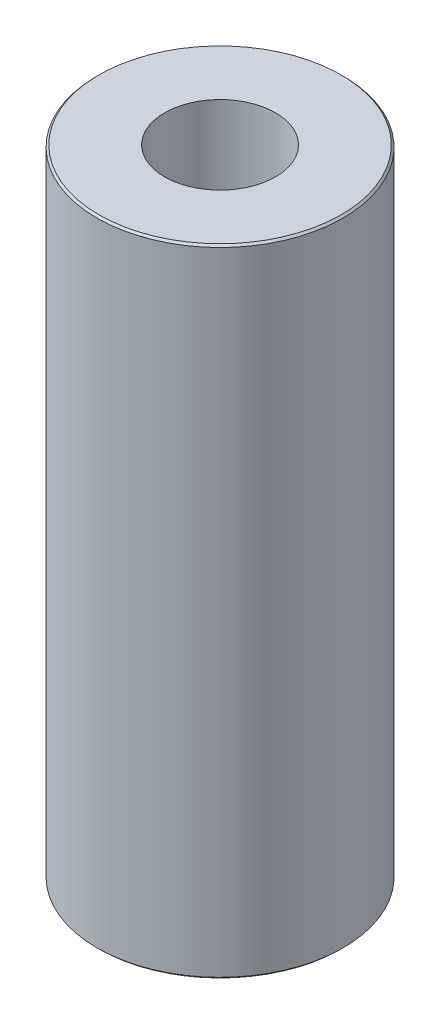
SolidWorks part; units mm, degrees
ref_plane "Front Plane" through (0, 0, 0) normal (0, 0, 1) x (1, 0, 0)
ref_plane "Top Plane" through (0, 0, 0) normal (0, 1, 0) x (1, 0, 0)
ref_plane "Right Plane" through (0, 0, 0) normal (1, 0, 0) x (0, 0, -1)
sketch "Sketch1" plane through (0, 0, 0) normal (0, 1, 0) x (1, 0, 0)
  circle A0 centre (0, 0) radius 35
  dimension "SHAFT_OD" = 70
extrude "Boss-Extrude1" add sketch "Sketch1" along normal blind 180.8649
sketch "Sketch2" plane through (0, 0, 0) normal (0, 1, 0) x (1, 0, 0)
  circle A0 centre (0, 0) radius 15.7892
  dimension "BORE_D" = 31.5784
extrude "Cut-Extrude1" cut sketch "Sketch2" along normal through all
chamfer "Chamfer1" distance 0.5475 angle 45 2 edges at (0, 180.8649, 35) (0, 0, 35)
